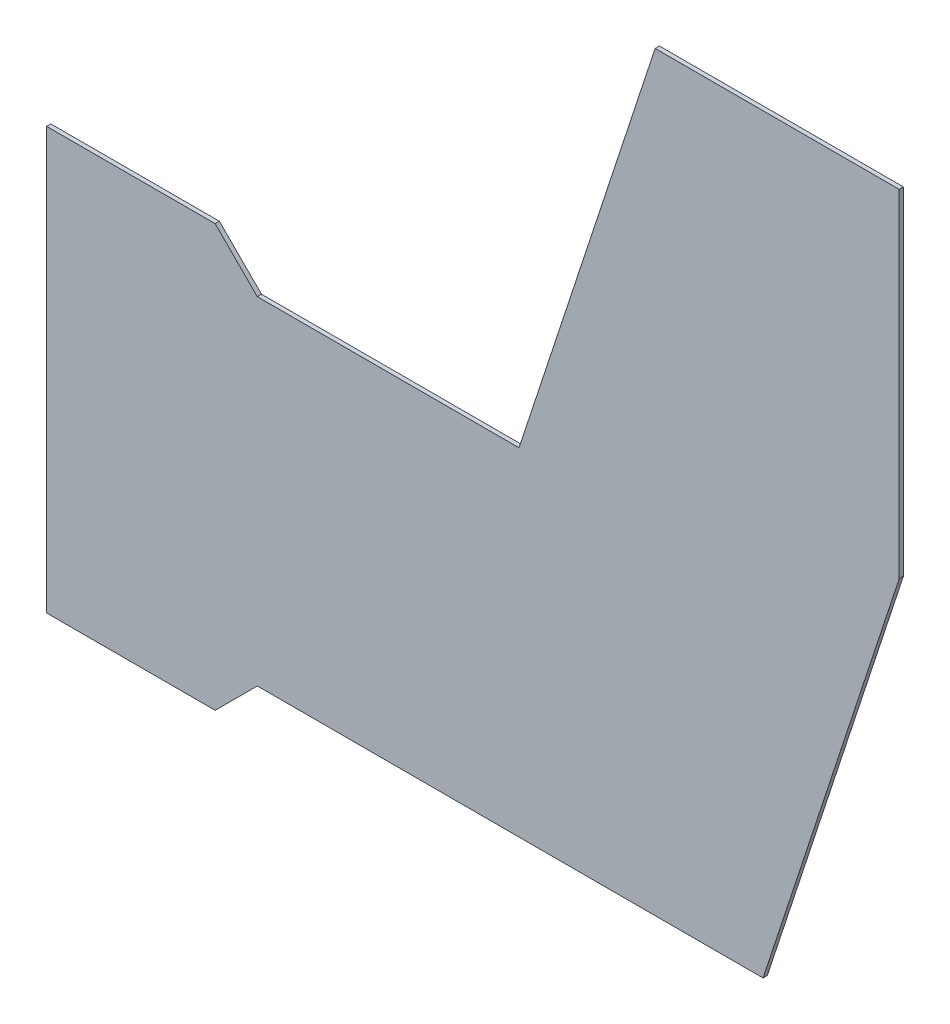
SolidWorks part; units mm, degrees
ref_plane "Front Plane" through (0, 0, 0) normal (0, 0, 1) x (1, 0, 0)
ref_plane "Top Plane" through (0, 0, 0) normal (0, 1, 0) x (1, 0, 0)
ref_plane "Right Plane" through (0, 0, 0) normal (1, 0, 0) x (0, 0, -1)
sketch "Sketch1" plane through (0, 0, 0) normal (0, 0, 1) x (1, 0, 0)
  line L2 (0, 0) -> (0, 254)
  line L5 (0, 0) -> (101.6, 0)
  line L6 (0, 254) -> (101.6, 254)
  line L8 (101.6, 0) -> (127, 25.4)
  line L9 (101.6, 254) -> (127, 228.6)
  line L10 (127, 25.4) -> (431.8, 25.4)
  line L14 (127, 228.6) -> (284.7259, 228.6)
  line L17 (431.8, 25.4) -> (513.8402, 274.828)
  line L19 (366.7661, 478.028) -> (513.8402, 478.028)
  line L20 (284.7259, 228.6) -> (366.7661, 478.028)
  line L21 (513.8402, 478.028) -> (513.8402, 274.828)
  dimension "D2" = 25.4
  dimension "D3" = 254
  dimension "D4" = 101.6
  dimension "D5" = 101.6
  dimension "D6" = 203.2
  dimension "D7" = 25.4
  dimension "D8" = 203.2
  dimension "D9" = 452.628
  dimension "D10" = 513.8402
  dimension "D11" = 304.8
  dimension "D12" = 203.2
  dimension "D13" = 262.5736
extrude "Boss-Extrude1" add sketch "Sketch1" along normal blind 2.54
